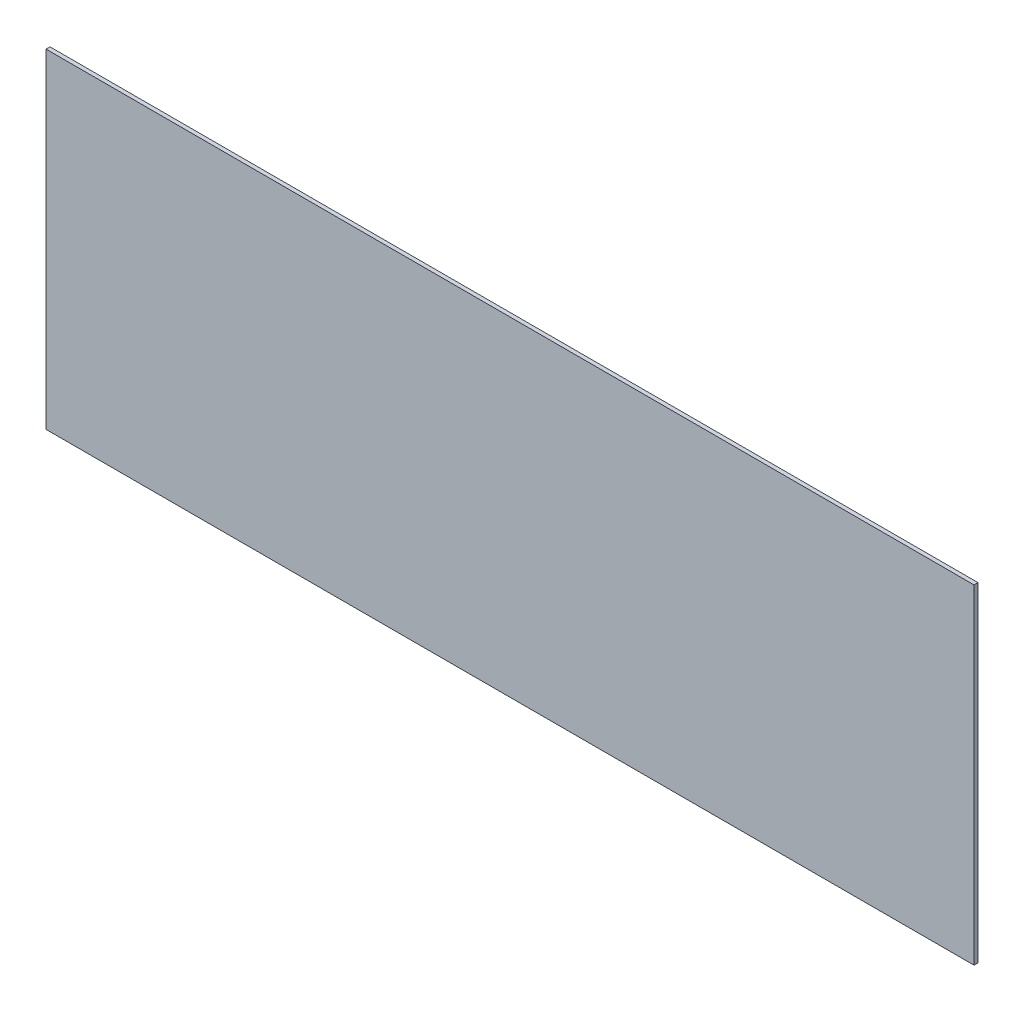
SolidWorks part; units mm, degrees
material "Mahogany"
ref_plane "Front Plane" through (0, 0, 0) normal (0, 0, 1) x (1, 0, 0)
ref_plane "Top Plane" through (0, 0, 0) normal (0, 1, 0) x (1, 0, 0)
ref_plane "Right Plane" through (0, 0, 0) normal (1, 0, 0) x (0, 0, -1)
sketch "Sketch1" plane through (0, 0, 0) normal (0, 0, 1) x (1, 0, 0)
  line L1 (-372.5, 132.2) -> (372.5, 132.2)
  line L2 (-372.5, 132.2) -> (-372.5, -132.2)
  line L3 (-372.5, -132.2) -> (372.5, -132.2)
  line L4 (372.5, 132.2) -> (372.5, -132.2)
  line L5 (-372.5, 132.2) -> (372.5, -132.2) construction
  line L6 (-372.5, -132.2) -> (372.5, 132.2) construction
  point P0 (0, 0)
  dimension "D1" = 745
  dimension "D2" = 264.4
extrude "Boss-Extrude1" add sketch "Sketch1" along normal blind 3.175
equation "\"W\"= 1700"
equation "\"L\"= 760"
equation "\"H\"= 810"
equation "\"ARM_BOLT_SPACING\"= 140"
equation "\"ARM_TO_WALL\"= 300"
equation "\"D1@Sketch1\"=\"L\"-15"
equation "\"D2@Sketch1\"=279.4-15"
